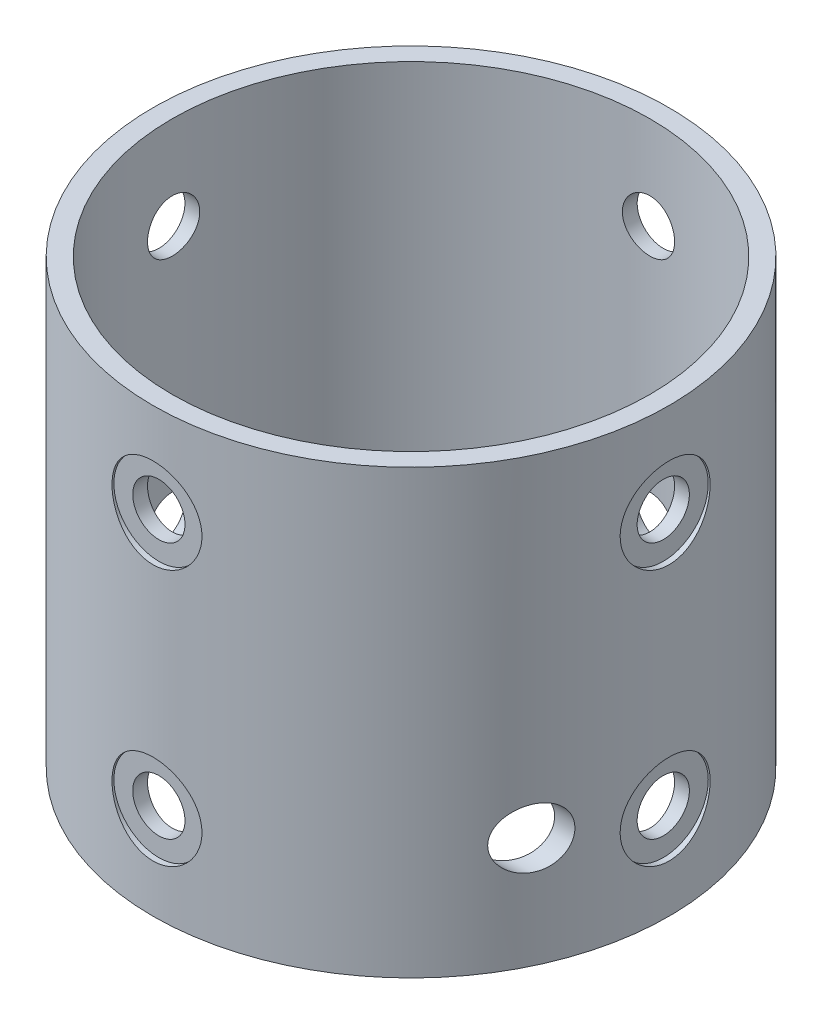
SolidWorks part; units mm, degrees
ref_plane "Front Plane" through (0, 0, 0) normal (1, 0, 0) x (0, 1, 0)
ref_plane "Top Plane" through (0, 0, 0) normal (0, 0, 1) x (0, 1, 0)
ref_plane "Right Plane" through (0, 0, 0) normal (0, 1, 0) x (-1, 0, 0)
sketch "Sketch1" plane through (0, 0, 0) normal (0, 1, 0) x (-1, 0, 0)
  circle A0 centre (0, 0) radius 22.225
  circle A1 centre (0, 0) radius 20.574
  point P4 (-22.225, 0)
  point P5 (-20.574, 0)
  dimension "D1" = 44.45
  dimension "D2" = 1.651
extrude "Boss-Extrude1" add sketch "Sketch1" along normal blind 38.1
sketch "Sketch2" plane through (0, 0, 0) normal (1, 0, 0) x (0, 1, 0)
  circle A0 centre (9.525, 9.525) radius 2.54
  dimension "D1" = 5.08
  dimension "D2" = 9.525
  dimension "D3" = 9.525
extrude "Cut-Extrude1" cut sketch "Sketch2" along normal blind 50.8
ref_plane "Plane1" through (0, 0, 22.225) normal (0, 0, 1) x (1, 0, 0)
sketch "Sketch3" plane through (0, 0, 22.225) normal (0, 0, 1) x (1, 0, 0)
  line L0 (20.574, 38.1) -> (-20.574, 38.1) construction
  line L1 (22.225, 38.1) -> (-22.225, 38.1) construction
  circle A0 centre (0, 30.1) radius 3.875
  circle A1 centre (0, 30.1) radius 2.25
  point P6 (0, 38.1)
  dimension "D1" = 7.75
  dimension "D3" = 4.5
  dimension "D2" = 8
extrude "Cut-Extrude2" cut sketch "Sketch3" against normal blind 0.5
extrude "Cut-Extrude3" cut sketch "Sketch3<2>" against normal blind 16.17 contours A1 region at (0, 30.1, 22.225)
sketch "Sketch3<2>" plane through (0, 0, 22.225) normal (0, 0, 1) x (1, 0, 0) same geometry as "Sketch3"
pattern_circular "CirPattern1" count 4 over 360 about axis through (0, 38.1, 0) along (0, -1, 0) of "Cut-Extrude2", "Cut-Extrude3"
ref_plane "Plane2" through (0, 19.05, 0) normal (0, -1, 0) x (-1, 0, 0)
mirror "Mirror1" about plane through (0, 19.05, 0) normal (0, -1, 0) of "CirPattern1"
